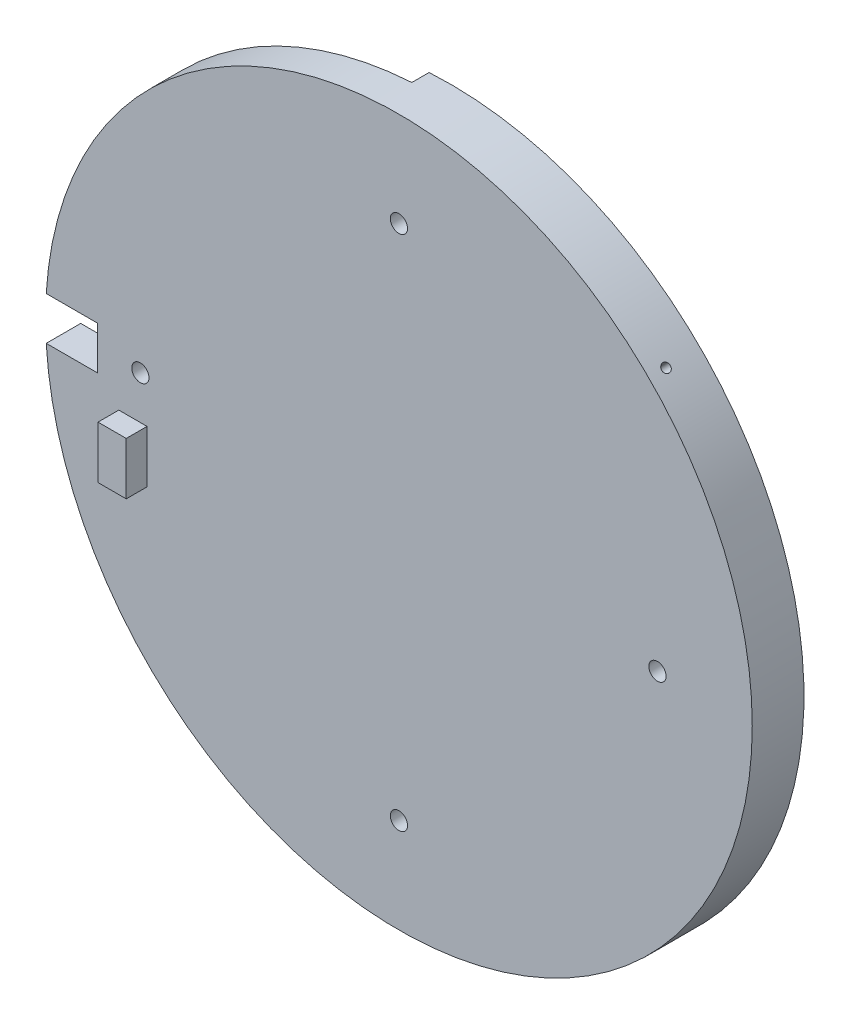
SolidWorks part; units mm, degrees
ref_plane "Front Plane" through (0, 0, 0) normal (0, 0, 1) x (1, 0, 0)
ref_plane "Top Plane" through (0, 0, 0) normal (0, 1, 0) x (1, 0, 0)
ref_plane "Right Plane" through (0, 0, 0) normal (1, 0, 0) x (0, 0, -1)
sketch "Sketch1" plane through (0, 0, 0) normal (0, 0, 1) x (1, 0, 0)
  circle A0 centre (0, 0) radius 82
  dimension "D1" = 164
extrude "Boss-Extrude1" add sketch "Sketch1" along normal blind 8
sketch "Sketch3" plane through (0, 0, 0) normal (0, 0, -1) x (-1, 0, 0)
  line L0 (5, 81.8474) -> (5, 75.3343)
  line L1 (5, -75.3343) -> (5, -81.8474)
  arc A0 (5, 75.3343) -> (5, -75.3343) centre (0, 0) ccw
  circle A1 centre (0, 0) radius 82 construction
  arc A2 (5, 81.8474) -> (5, -81.8474) centre (0, 0) ccw
  dimension "D1" = 151
  dimension "D2" = 5
extrude "Boss-Extrude3" add sketch "Sketch3" along normal blind 4
fillet "Fillet1" radius 5 2 edges at (-5, 75.3343, -2) (-5, -75.3343, -2)
sketch "Sketch2" plane through (0, 0, 8) normal (0, 0, 1) x (1, 0, 0)
  circle A0 centre (0, 60) radius 2
  dimension "D1" = 4
  dimension "D2" = 60
extrude "Cut-Extrude1" cut sketch "Sketch2" against normal blind 15
pattern_circular "CirPattern2" count 4 every 90 about axis through (0, 0, 0) along (0, 0, 1) of "Cut-Extrude1"
sketch "Sketch7" plane through (0, 0, 0) normal (0, 0, -1) x (-1, 0, 0)
  line L7 (1.7885, 63.6242) -> (-2.2444, 63.3609)
  line L8 (-2.2444, 63.3609) -> (-4.0329, 59.7368)
  line L9 (-4.0329, 59.7368) -> (-1.7885, 56.3758)
  line L10 (-1.7885, 56.3758) -> (2.2444, 56.6391)
  line L11 (2.2444, 56.6391) -> (4.0329, 60.2632)
  line L12 (4.0329, 60.2632) -> (1.7885, 63.6242)
  circle A0 centre (0, 60) radius 3.5 construction
  point P30 (36.3101, 9.0679)
  dimension "D1" = 7
extrude "Cut-Extrude3" cut sketch "Sketch7" against normal blind 3.2
sketch "Sketch9" plane through (0, 0, 8) normal (0, 0, 1) x (1, 0, 0)
  line L0 (-80, 5) -> (-82.5116, 5)
  line L1 (-80, 5) -> (-70, 5)
  line L2 (-80, 5) -> (-80, -5)
  line L3 (-80, -5) -> (-70, -5)
  line L4 (-70, 5) -> (-70, -5)
  line L5 (-80, 5) -> (-70, -5) construction
  line L6 (-80, -5) -> (-70, 5) construction
  line L7 (-82.5116, 5) -> (-82.5116, -5)
  line L8 (-82.5116, -5) -> (-80, -5)
  circle A0 centre (0, 0) radius 82 construction
  point P0 (-75, 0)
  circle M6 centre (0, 0) radius 82
  dimension "D2" = 75
  dimension "D1" = 10
  dimension "D3" = 10
extrude "Cut-Extrude4" cut sketch "Sketch9" against normal blind 22.2 contours L8 L2 L0 M6 | L7 L8 L0 M6 | L4 L1 L2 L3 region at (-80.9751, 0, 8) region at (-75, 0, 8) region at (-82.2285, 0, 8)
pattern_circular "CirPattern3" count 4 every 90 about axis through (0, 0, 0) along (0, 0, 1) of "Cut-Extrude3"
ref_plane "Plane1" through (0, 0, 0) normal (-0.7071, 0.7071, 0) x (0.7071, 0.7071, 0)
ref_plane "Plane2" through (-57.9828, 57.9828, 0) normal (-0.7071, 0.7071, 0) x (0.7071, 0.7071, 0)
sketch "Sketch10" plane through (-57.9828, 57.9828, 0) normal (-0.7071, 0.7071, 0) x (0.7071, 0.7071, 0)
  line L0 (75.5, 0) -> (-53.3866, 0) construction
  circle A0 centre (0, -4) radius 1
  dimension "D1" = 2
  dimension "D2" = 4
extrude "Cut-Extrude5" cut sketch "Sketch10" against normal blind 12
pattern_circular "CirPattern4" count 4 every 90 about axis through (0, 0, 0) along (0, 0, 1) of "Cut-Extrude5"
sketch "Sketch12" plane through (0, 0, 8) normal (0, 0, 1) x (1, 0, 0)
  line L0 (-81.8474, -5) -> (-70, -5) construction
  line L1 (-65, -10) -> (-58.4513, -10)
  line L2 (-65, -10) -> (-65, -22.15)
  line L3 (-65, -22.15) -> (-58.4513, -22.15)
  line L4 (-58.4513, -10) -> (-58.4513, -22.15)
  line L6 (-70, 5) -> (-70, -5) construction
  dimension "D1" = 5
  dimension "D2" = 12.15
  dimension "D3" = 5
extrude "Boss-Extrude4" add sketch "Sketch12" along normal blind 4.83
sketch "Sketch13" plane through (-65, 0, 0) normal (-1, 0, 0) x (0, 0, 1)
  line L0 (12.83, -10) -> (12.83, -22.15) construction
  circle A0 centre (10.38, -15.4388) radius 1.25
  dimension "D2" = 2.5
  dimension "D1" = 2.45
extrude "Cut-Extrude6" cut sketch "Sketch13" against normal blind 4.83
